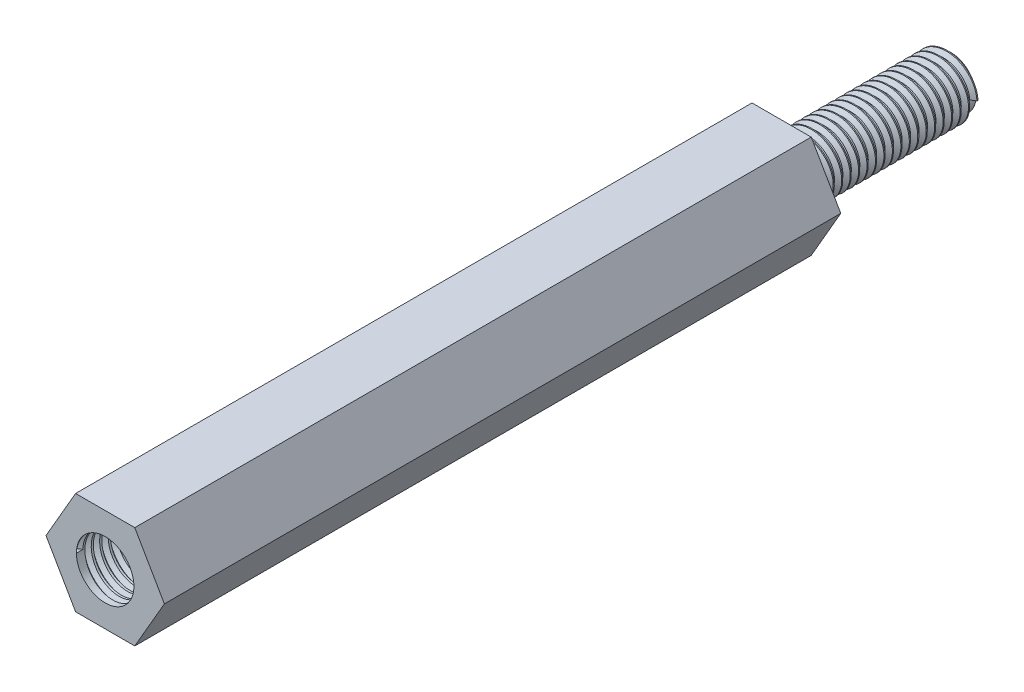
SolidWorks part; units mm, degrees
material "1.7036 (28CrS4)"
ref_plane "Plan de face" through (0, 0, 0) normal (0, 0, 1) x (1, 0, 0)
ref_plane "Plan de dessus" through (0, 0, 0) normal (0, 1, 0) x (1, 0, 0)
ref_plane "Plan de droite" through (0, 0, 0) normal (1, 0, 0) x (0, 0, -1)
sketch "Esquisse1" plane through (0, 0, 0) normal (0, 0, 1) x (1, 0, 0)
  line L0 (0, 3.5) -> (7, 3.5) construction
  line L1 (0, 0) -> (7, 0) construction
  line L2 (0, 0) -> (0, 7) construction
  line L3 (0, 7) -> (7, 7) construction
  line L4 (7, 0) -> (7, 7) construction
  line L5 (3.5, 7) -> (3.5, 0) construction
  line L7 (5.25, 0.4689) -> (7, 3.5)
  line L8 (7, 3.5) -> (5.25, 6.5311)
  line L9 (5.25, 6.5311) -> (1.75, 6.5311)
  line L10 (1.75, 6.5311) -> (0, 3.5)
  line L11 (0, 3.5) -> (1.75, 0.4689)
  line L12 (1.75, 0.4689) -> (5.25, 0.4689)
  circle A0 centre (3.5, 3.5) radius 3.5 construction
  dimension "D3" = 7
  dimension "D1" = 7
  dimension "D2" = 7
extrude "Boss.-Extru.1" add sketch "Esquisse1" along normal blind 50
sketch "Esquisse2" plane through (0, 0, 50) normal (0, 0, 1) x (1, 0, 0)
  line L0 (3.5, 6.5311) -> (3.5, 0.4689) construction
  line L1 (0.875, 1.9845) -> (6.125, 5.0155) construction
  line L6 (1.75, 0.4689) -> (5.25, 0.4689)
  line L7 (5.25, 0.4689) -> (7, 3.5)
  line L8 (7, 3.5) -> (5.25, 6.5311)
  line L9 (5.25, 6.5311) -> (1.75, 6.5311)
  line L10 (1.75, 6.5311) -> (0, 3.5)
  line L11 (0, 3.5) -> (1.75, 0.4689)
  line L12 (1.75, 0.4689) -> (5.25, 0.4689)
  line L13 (5.25, 0.4689) -> (7, 3.5)
  line L14 (7, 3.5) -> (5.25, 6.5311)
  line L15 (5.25, 6.5311) -> (1.75, 6.5311)
  line L16 (1.75, 6.5311) -> (0, 3.5)
  line L17 (0, 3.5) -> (1.75, 0.4689)
  circle A0 centre (3.5, 3.5) radius 1.5
  dimension "D2" = 3
  dimension "D1" = 0
hole_wizard "Dégagement M31" positions "Esquisse6" profile "Esquisse7" hole size "M3" standard "ISO"
sketch "Esquisse6" plane through (0, 0, 50) normal (0, 0, 1) x (1, 0, 0)
  point P0 (3.5, 3.5)
sketch "Esquisse7" plane through (3.5, 3.5, 50) normal (1, 0, 0) x (0, -1, 0)
  line L0 (0, 0) -> (0, 11.0215)
  line L1 (0, 11.0215) -> (1.7, 10)
  line L2 (1.7, 10) -> (1.7, 0)
  line L5 (1.7, 0) -> (0, 0)
  line L10 (0, 11.0215) -> (-1.7, 10) construction
  line L11 (0, -6.35) -> (0, 107.95) construction
  dimension "Diamètre du perçage" = 3.4
  dimension "Profondeur du perçage" = 10
  dimension "Angle de pointe" = 118
thread "Filetage1" pitch 0.5 start angle 0, offset 0, length 15, pitch 0.5, diameter 3.4
ref_plane "Plan1" through (1.8, 3.5, 50) normal (0, -1, 0) x (-1, 0, 0)
sketch "Profil de filetage1" plane through (1.8, 3.5, 50) normal (0, -1, 0) x (-1, 0, 0)
  line L0 (0, 0) -> (0, 0.5) construction
  line L1 (0, 0) -> (0.2706, 0.1562)
  line L2 (0.2706, 0.1562) -> (0.2706, 0.2187)
  line L3 (0.2706, 0.2187) -> (0, 0.375)
  line L4 (0.2706, 0.1875) -> (0, 0.1875) construction
  line L11 (0, 0) -> (0, 0.375)
  point P2 (0, 0)
  dimension "Pitch" = 0.5
  dimension "Profile_Angle" = 60
  dimension "Profile_Land" = 0.0625
  dimension "Profile_Height" = 0.2706
hole_wizard "Dégagement M32" [suppressed] positions "Esquisse10" profile "Esquisse11" hole size "M3" standard "ISO"
sketch "Esquisse10" plane through (0, 0, 0) normal (0, 0, -1) x (-1, 0, 0)
  point P0 (-3.5, 3.5)
sketch "Esquisse11" plane through (3.5, 3.5, 0) normal (1, 0, 0) x (0, 1, 0)
  line L0 (0, 0) -> (0, 9.0215)
  line L1 (0, 9.0215) -> (1.7, 8)
  line L2 (1.7, 8) -> (1.7, 0)
  line L5 (1.7, 0) -> (0, 0)
  line L10 (0, 9.0215) -> (-1.7, 8) construction
  line L11 (0, -6.35) -> (0, 107.95) construction
  dimension "Diamètre du perçage" = 3.4
  dimension "Profondeur du perçage" = 8
  dimension "Angle de pointe" = 118
sketch "Esquisse12" plane through (0, 0, 0) normal (0, 0, -1) x (-1, 0, 0)
  line L6 (-5.25, 0.4689) -> (-1.75, 0.4689)
  line L7 (-1.75, 0.4689) -> (0, 3.5)
  line L8 (0, 3.5) -> (-1.75, 6.5311)
  line L9 (-1.75, 6.5311) -> (-5.25, 6.5311)
  line L10 (-5.25, 6.5311) -> (-7, 3.5)
  line L11 (-7, 3.5) -> (-5.25, 0.4689)
  line L12 (-5.25, 0.4689) -> (-1.75, 0.4689)
  line L13 (-1.75, 0.4689) -> (0, 3.5)
  line L14 (0, 3.5) -> (-1.75, 6.5311)
  line L15 (-1.75, 6.5311) -> (-5.25, 6.5311)
  line L16 (-5.25, 6.5311) -> (-7, 3.5)
  line L17 (-7, 3.5) -> (-5.25, 0.4689)
  circle A0 centre (-3.5, 3.5) radius 1.5
  dimension "D2" = 3
  dimension "D1" = 0
extrude "Enlèv. mat.-Extru.1" cut sketch "Esquisse12" against normal blind 10
thread "Filetage2" pitch 0.5 profile "Profil de filetage2" start angle 0, offset 0, length 15, pitch 0.5, diameter 3
ref_plane "Plan2" through (5, 3.5, 0) normal (0, -1, 0) x (1, 0, 0)
sketch "Profil de filetage2" plane through (5, 3.5, 0) normal (0, -1, 0) x (1, 0, 0)
  line L0 (0, 0) -> (0, 0.5) construction
  line L1 (0, 0) -> (0.2706, 0.1562)
  line L2 (0.2706, 0.1562) -> (0.2706, 0.2187)
  line L3 (0.2706, 0.2187) -> (0, 0.375)
  line L4 (0.2706, 0.1875) -> (0, 0.1875) construction
  line L11 (0, 0) -> (0, 0.375)
  point P2 (0, 0)
  dimension "Pitch" = 0.5
  dimension "Profile_Angle" = 60
  dimension "Profile_Land" = 0.0625
  dimension "Profile_Height" = 0.2706
equation "\"diam_cercle_circons\"= 7"
equation "\"D1@Esquisse1\"=\"diam_cercle_circons\""
equation "\"D2@Esquisse1\"=\"diam_cercle_circons\""
equation "\"Hauteur\" = 35 + 15"
equation "\"D1@Boss.-Extru.1\"=\"Hauteur\""
equation "\"D3@Esquisse1\"=\"diam_cercle_circons\""
